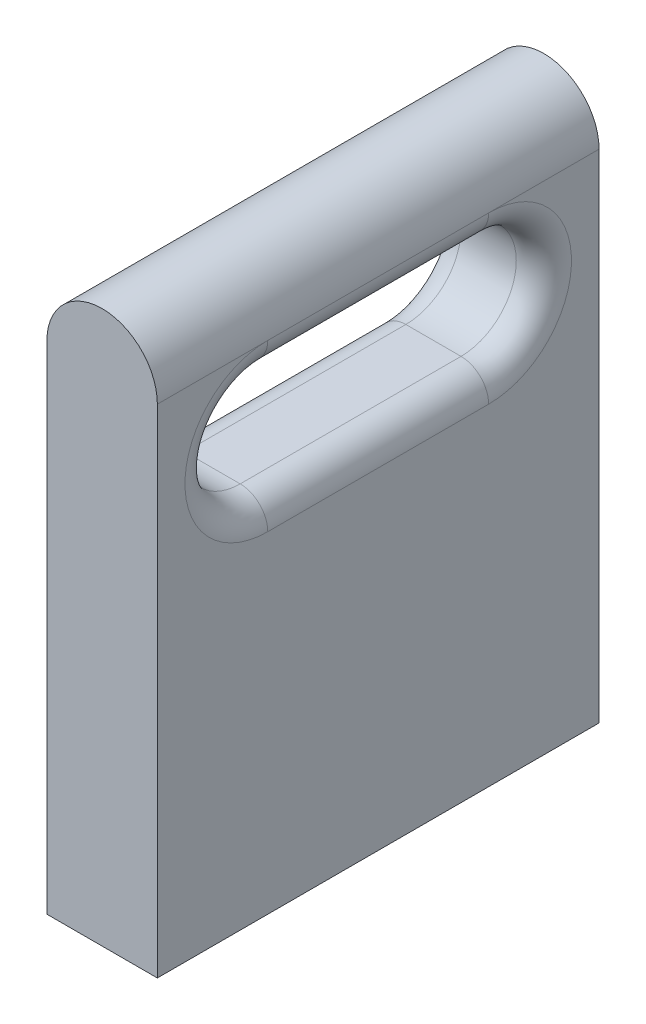
SolidWorks part; units mm, degrees
ref_plane "Front Plane" through (0, 0, 0) normal (0, 0, 1) x (1, 0, 0)
ref_plane "Top Plane" through (0, 0, 0) normal (0, 1, 0) x (1, 0, 0)
ref_plane "Right Plane" through (0, 0, 0) normal (1, 0, 0) x (0, 0, -1)
sketch "Sketch1" plane through (0, 0, 0) normal (0, 0, 1) x (1, 0, 0)
  line L0 (0, 0) -> (25.4, 0)
  line L1 (25.4, 0) -> (25.4, 114.3)
  line L2 (0, 0) -> (0, 114.3)
  arc A0 (0, 114.3) -> (25.4, 114.3) centre (12.7, 114.3) cw
  point P6 (12.7, 127)
  dimension "D1" = 25.4
  dimension "D2" = 127
extrude "Boss-Extrude1" add sketch "Sketch1" along normal blind 101.6
sketch "Sketch2" plane through (25.4, 0, 0) normal (1, 0, 0) x (0, 0, -1)
  line L0 (-76.2, 95.25) -> (-25.4, 95.25) construction
  line L1 (-76.2, 107.95) -> (-25.4, 107.95)
  line L2 (-76.2, 82.55) -> (-25.4, 82.55)
  line L4 (-101.6, 0) -> (0, 0) construction
  line L6 (-88.9, 95.25) -> (-101.6, 95.25) construction
  line L7 (-101.6, 0) -> (-101.6, 114.3) construction
  arc A0 (-76.2, 107.95) -> (-76.2, 82.55) centre (-76.2, 95.25) ccw
  arc A1 (-25.4, 82.55) -> (-25.4, 107.95) centre (-25.4, 95.25) ccw
  point P2 (-50.8, 95.25)
  point P15 (-12.7, 95.25)
  dimension "D2" = 12.7
  dimension "D1" = 82.55
  dimension "D3" = 12.7
  dimension "D4" = 76.2
extrude "Cut-Extrude1" cut sketch "Sketch2" against normal through all both and the other way through all contours L1 A1 L2 A0
fillet "Fillet6" radius 6.35 4 edges at (0, 95.25, 88.9) (0, 107.95, 50.8) (0, 95.25, 12.7) (0, 82.55, 50.8)
fillet "Fillet7" radius 6.35 4 edges at (25.4, 95.25, 12.7) (25.4, 107.95, 50.8) (25.4, 95.25, 88.9) (25.4, 82.55, 50.8)
